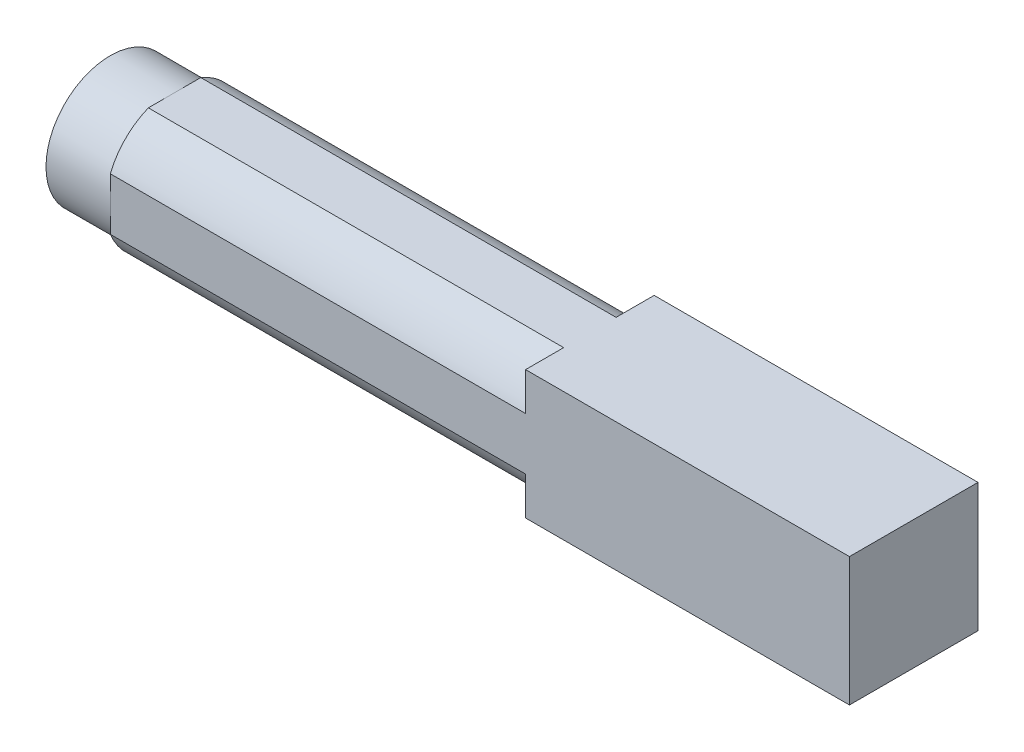
SolidWorks part; units mm, degrees
ref_plane "Front Plane" through (0, 0, 0) normal (0, 0, 1) x (1, 0, 0)
ref_plane "Top Plane" through (0, 0, 0) normal (0, 1, 0) x (1, 0, 0)
ref_plane "Right Plane" through (0, 0, 0) normal (1, 0, 0) x (0, 0, -1)
sketch "Sketch1" plane through (0, 0, 0) normal (1, 0, 0) x (0, 0, -1)
  line L1 (-3.175, -3.175) -> (3.175, -3.175)
  line L2 (-3.175, -3.175) -> (-3.175, 3.175)
  line L3 (-3.175, 3.175) -> (3.175, 3.175)
  line L4 (3.175, -3.175) -> (3.175, 3.175)
  line L5 (-3.175, -3.175) -> (3.175, 3.175) construction
  line L6 (-3.175, 3.175) -> (3.175, -3.175) construction
  point P0 (0, 0)
  dimension "D1" = 6.35
extrude "Boss-Extrude1" add sketch "Sketch1" along normal blind 39.6875
ref_axis "Axis1" through (0, 0, 0) along (1, 0, 0)
ref_plane "Plane1" through (24.0716, 0, 0) normal (-1, 0, 0) x (0, 0, 1)
sketch "Sketch4" plane through (0, 0, 0) normal (-1, 0, 0) x (0, 0, 1)
  line L1 (-5.5323, -4.0531) -> (5.5323, -4.0531)
  line L2 (-5.5323, -4.0531) -> (-5.5323, 4.0531)
  line L3 (-5.5323, 4.0531) -> (5.5323, 4.0531)
  line L4 (5.5323, -4.0531) -> (5.5323, 4.0531)
  line L5 (-5.5323, -4.0531) -> (5.5323, 4.0531) construction
  line L6 (-5.5323, 4.0531) -> (5.5323, -4.0531) construction
  circle A0 centre (0, 0) radius 3.175
  dimension "D1" = 6.35
extrude "Cut-Extrude3" cut sketch "Sketch4" against normal blind 3.175
sketch "Sketch5" plane through (3.175, 0, 0) normal (-1, 0, 0) x (0, 0, 1)
  line L1 (-4.6082, -4.6911) -> (4.6082, -4.6911)
  line L2 (-4.6082, -4.6911) -> (-4.6082, 4.6911)
  line L3 (-4.6082, 4.6911) -> (4.6082, 4.6911)
  line L4 (4.6082, -4.6911) -> (4.6082, 4.6911)
  line L5 (-4.6082, -4.6911) -> (4.6082, 4.6911) construction
  line L6 (-4.6082, 4.6911) -> (4.6082, -4.6911) construction
  circle A0 centre (0, 0) radius 3.429
  dimension "D1" = 6.858
extrude "Cut-Extrude4" cut sketch "Sketch5" against normal up to surface (20.5156 mm away)
